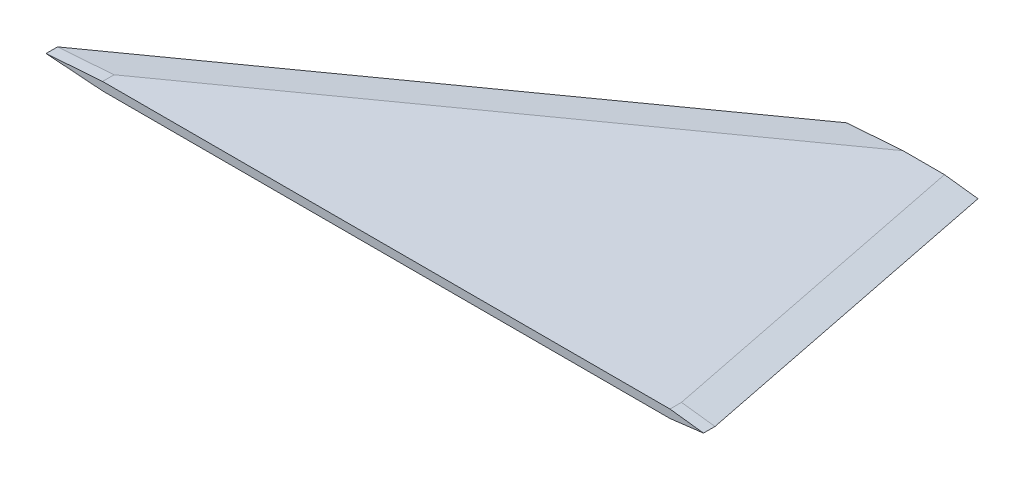
SolidWorks part; units mm, degrees
material "6061-T6 (SS)"
ref_plane "Front Plane" through (0, 0, 0) normal (0, 0, 1) x (1, 0, 0)
ref_plane "Top Plane" through (0, 0, 0) normal (0, 1, 0) x (1, 0, 0)
ref_plane "Right Plane" through (0, 0, 0) normal (1, 0, 0) x (0, 0, -1)
sketch "Sketch1" plane through (0, 0, 0) normal (0, 1, 0) x (1, 0, 0)
  line L0 (-127, 0) -> (127, 0)
  line L1 (-127, 0) -> (50.8, 127)
  line L2 (50.8, 127) -> (101.6, 127)
  line L3 (101.6, 127) -> (127, 0)
  point P3 (0, 0)
  dimension "D1" = 254
  dimension "D2" = 127
  dimension "D3" = 50.8
  dimension "D4" = 177.8
extrude "Boss-Extrude1" add sketch "Sketch1" along normal mid plane 3.175
chamfer "Chamfer1" distance 12.7 distance2 1.5875 2 edges at (-38.1, 1.5875, -63.5) (-38.1, -1.5875, -63.5) first distance on face at (38.1, 1.5875, -63.5) first distance on face at (38.1, -1.5875, -63.5)
chamfer "Chamfer2" distance 12.7 distance2 1.5875 2 edges at (114.3, 1.5875, -63.5) (114.3, -1.5875, -63.5) first distance on face at (49.025, 1.5875, -63.5) first distance on face at (49.025, -1.5875, -63.5)
sketch "Sketch2" plane through (0, 0, 0) normal (0, 0, 1) x (1, 0, 0)
  line L4 (-105.1501, -1.5875) -> (114.0485, -1.5875)
  line L5 (114.0485, -1.5875) -> (127, 0)
  line L6 (114.0485, 1.5875) -> (-105.1501, 1.5875)
  line L7 (114.0485, -1.5875) -> (127, 0)
  line L8 (-105.1501, -1.5875) -> (114.0485, -1.5875)
  line L9 (127, 0) -> (114.0485, 1.5875)
  line L10 (114.0485, 1.5875) -> (-105.1501, 1.5875)
  line L11 (127, 0) -> (114.0485, 1.5875)
  line L14 (-105.1501, 1.5875) -> (-127, 0)
  line L15 (-105.1501, 1.5875) -> (-127, 0)
  line L16 (-127, 0) -> (-105.1501, -1.5875)
  line L17 (-127, 0) -> (-105.1501, -1.5875)
  dimension "D1" = 0
extrude "Boss-Extrude3" add sketch "Sketch2" along normal blind 4.445
